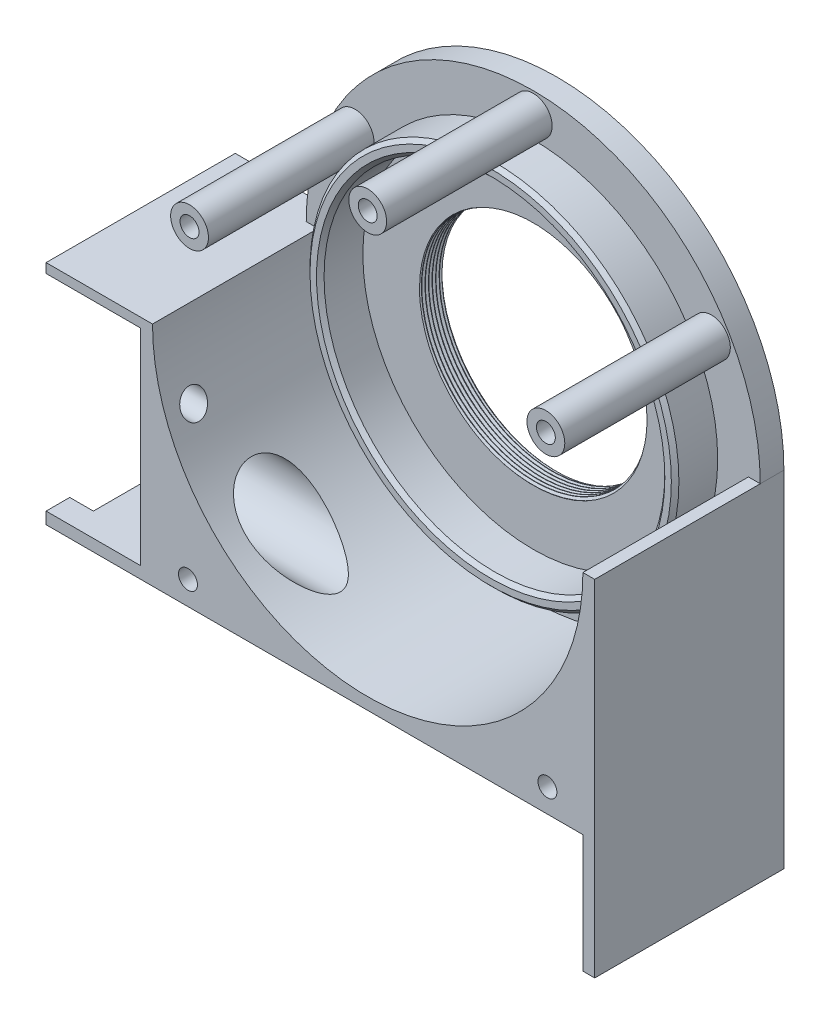
SolidWorks part; units mm, degrees
ref_plane "Plan de face" through (0, 0, 0) normal (0, 0, 1) x (1, 0, 0)
ref_plane "Plan de dessus" through (0, 0, 0) normal (0, 1, 0) x (1, 0, 0)
ref_plane "Plan de droite" through (0, 0, 0) normal (1, 0, 0) x (0, 0, -1)
sketch "Esquisse1" plane through (0, 0, 0) normal (0, 0, 1) x (1, 0, 0)
  circle A0 centre (0, 0) radius 23.8
  circle A1 centre (0, 0) radius 48
  dimension "D1" = 47.6
  dimension "D2" = 96
extrude "Boss.-Extru.1" add sketch "Esquisse1" along normal blind 40
sketch "Esquisse2" plane through (0, 0, 40) normal (0, 0, 1) x (1, 0, 0)
  circle A0 centre (0, 0) radius 45.5
  circle A1 centre (0, 0) radius 48 construction
  dimension "D1" = 2.5
extrude "Enlèv. mat.-Extru.1" cut sketch "Esquisse2" against normal blind 35
chamfer "Chanfrein2" distance 0.5 angle 45 1 edges at (23.8, 0, 0)
sketch "Esquisse14" plane through (0, 0, 0) normal (0, 0, 1) x (1, 0, 0)
  circle A0 centre (0, 0) radius 24.5
curve "Hélice/Spirale1" pitch 0.75 height 7.5 turns 10
sketch "Esquisse15" plane through (0, 0, 0) normal (-1, 0, 0) x (0, 0, 1)
  line L4 (0.501, -22.0731) -> (0.501, -22.5925) construction
  line L9 (0.8323, -23.8) -> (0.1698, -23.8)
  line L10 (0.1698, -23.8) -> (0.4573, -24.298)
  line L11 (0.4573, -24.298) -> (0.5448, -24.298)
  line L12 (0.8323, -23.8) -> (0.5448, -24.298)
  point P7 (0.501, -24.298)
  point P8 (0.501, -23.8)
  dimension "D1" = 60
  dimension "D2" = 0.0875
  dimension "D3" = 23.8
  dimension "D6" = 0.6625
sweep "Enlèvement de matière-Balayage1" cut profiles "Esquisse15" path "Hélice/Spirale1"
sketch "Esquisse23" plane through (0, 0, 40) normal (0, 0, 1) x (1, 0, 0)
  line L0 (-43.942, 0) -> (-49.526, 0)
  line L2 (43.942, 0) -> (49.526, 0)
  arc A0 (49.526, 0) -> (-49.526, 0) centre (0, 0) ccw
  arc A1 (43.942, 0) -> (-43.942, 0) centre (0, 0) ccw
extrude "Enlèv. mat.-Extru.6" cut sketch "Esquisse23" against normal up to surface (35 mm away) up to face at (-0.0839, -0.1997, 5)
sketch "Esquisse27" plane through (0, 0, 0) normal (1, 0, 0) x (0, 0, -1)
  circle A0 centre (-27.5, -34) radius 7.675
  dimension "D1" = 27.5
  dimension "D3" = 15.35
  dimension "D2" = 34
extrude "Enlèv. mat.-Extru.7" cut sketch "Esquisse27" against normal through all
sketch3d "Esquisse3D2" plane through (0, 0, 0) normal (0, 0, 1) x (1, 0, 0)
  dimension "D1" = 48
sketch "Esquisse33" plane through (-48, 0, 0) normal (1, 0, 0) x (0, 0, -1)
  line L0 (-24.2366, -37.2634) -> (-32.0205, -29.4795) construction
  line L1 (13.3219, -63.5082) -> (-63.8041, 13.6179) construction
  line L2 (-27.5, -34) -> (-32.3825, -38.8825) construction
  line L3 (-40, -48) -> (-40, 9.0935) construction
  line L5 (-40, -48) -> (0, -48)
  line L6 (-40, -48) -> (-40, 0)
  line L7 (-40, 0) -> (0, 0)
  line L8 (0, -48) -> (0, 0)
  circle A0 centre (-27.5, -34) radius 7.675
  circle A1 centre (-34.2175, -15.9688) radius 2.75
  circle A2 centre (-9.4688, -40.7175) radius 2.75
  dimension "D1" = 8
  dimension "D2" = 5.5
  dimension "D3" = 17.5
  dimension "D5" = 45
extrude "Boss.-Extru.5" add sketch "Esquisse33" along normal up to next
sketch "Esquisse35" plane through (-48, 0, 0) normal (-1, 0, 0) x (0, 0, 1)
  circle A0 centre (34.2175, -15.9688) radius 2.75
  circle A1 centre (9.4688, -40.7175) radius 2.75
extrude "Enlèv. mat.-Extru.12" cut sketch "Esquisse35" against normal blind 16
sketch "Esquisse36" plane through (-48, 0, 0) normal (-1, 0, 0) x (0, 0, 1)
  line L0 (2.5, 0) -> (0, 0)
  line L1 (0, 0) -> (5, 0) construction
  line L2 (0, 0) -> (0, -48)
  line L3 (0, -48) -> (0, 0) construction
  line L4 (0, -48) -> (40, -48)
  line L5 (40, -48) -> (0, -48) construction
  line L6 (40, -48) -> (40, -45.5)
  line L7 (40, -45.5) -> (2.5, -45.5)
  line L8 (2.5, -45.5) -> (2.5, 0)
  dimension "D1" = 2.5
extrude "Boss.-Extru.6" add sketch "Esquisse36" along normal blind 20
sketch "Esquisse37" plane through (0, -48, 0) normal (0, -1, 0) x (1, 0, 0)
  line L0 (0, 0) -> (0, 40) construction
  line L1 (-68, 0) -> (0, 0)
  line L2 (-68, 0) -> (-68, 2.5)
  line L3 (-68, 2.5) -> (0, 2.5)
  line L4 (0, 0) -> (0, 2.5)
  dimension "D1" = 2.5
extrude "Boss.-Extru.7" add sketch "Esquisse37" along normal blind 25
sketch "Esquisse43" plane through (0, 0, 40) normal (0, 0, 1) x (1, 0, 0)
  line L0 (0, -45.5) -> (0, -48)
  line L1 (45.5, 0) -> (48, 0)
  line L2 (48, 0) -> (48, -48)
  line L4 (0, -48) -> (48, -48)
  arc A0 (-45.5, 0) -> (45.5, 0) centre (0, 0) ccw construction
  arc A1 (0, -45.5) -> (45.5, 0) centre (0, 0) ccw
extrude "Boss.-Extru.10" add sketch "Esquisse43" against normal up to surface (40 mm away) up to face at (24.3, 0, 0)
sketch "Esquisse45" plane through (0, -48, 0) normal (0, -1, 0) x (1, 0, 0)
  line L0 (48, 0) -> (48, 40) construction
  line L1 (0, 0) -> (48, 0)
  line L2 (0, 0) -> (0, 2.5)
  line L3 (0, 2.5) -> (45.5, 2.5)
  line L4 (48, 0) -> (48, 2.5)
  line L5 (48, 40) -> (-68, 40) construction
  line L7 (48, 2.5) -> (48, 40)
  line L8 (48, 40) -> (45.5, 40)
  line L9 (45.5, 2.5) -> (45.5, 40)
  dimension "D1" = 2.5
extrude "Boss.-Extru.11" add sketch "Esquisse45" along normal up to surface (25 mm away) up to face at (-34, -73, 1.25)
sketch "Esquisse46" plane through (0, 0, 40) normal (0, 0, 1) x (1, 0, 0)
  line L0 (-58.2365, -43) -> (69.7757, -43) construction
  line L1 (45.5, -48) -> (-68, -48) construction
  line L2 (-48, -45.5) -> (-48, 0) construction
  line L3 (48, -73) -> (48, 0) construction
  circle A0 centre (-38, -43) radius 2
  circle A1 centre (38, -43) radius 2
  dimension "D2" = 4
  dimension "D3" = 10
  dimension "D4" = 4
  dimension "D5" = 10
  dimension "D1" = 5
extrude "Enlèv. mat.-Extru.14" cut sketch "Esquisse46" against normal blind 5
sketch "Esquisse47" plane through (0, 0, 5) normal (0, 0, 1) x (1, 0, 0)
  circle A0 centre (0, 0) radius 36.025
  circle A1 centre (0, 0) radius 39
  dimension "D1" = 72.05
  dimension "D2" = 78
extrude "Boss.-Extru.12" add sketch "Esquisse47" along normal blind 9
sketch "Esquisse48" plane through (0, -48, 0) normal (0, -1, 0) x (1, 0, 0)
  line L5 (-68, 21.25) -> (-31.7445, 21.25) construction
  line L6 (-68, 2.5) -> (-68, 40) construction
  line L7 (45.5, 40) -> (-68, 40) construction
  line L8 (-73, 7.5) -> (-63, 7.5)
  line L9 (-73, 7.5) -> (-73, 35)
  line L10 (-73, 35) -> (-63, 35)
  line L11 (-63, 7.5) -> (-63, 35)
  line L12 (-73, 7.5) -> (-63, 35) construction
  line L13 (-73, 35) -> (-63, 7.5) construction
  dimension "D1" = 5
  dimension "D2" = 5
extrude "Enlèv. mat.-Extru.15" cut sketch "Esquisse48" against normal blind 9
chamfer "Chanfrein3" distance 0.8 angle 45 2 edges at (36.025, 0, 14) (39, 0, 14)
sketch "Esquisse49" plane through (0, 0, 5) normal (0, 0, 1) x (1, 0, 0)
  line L0 (0, 0) -> (-55.4935, 32.0392) construction
  line L1 (-68, 0) -> (-48, 0) construction
  line L2 (0, 0) -> (-37.6721, 21.75) construction
  line L3 (0, 0) -> (0, 43.5) construction
  circle A0 centre (-37.6721, 21.75) radius 2
  circle A2 centre (-37.6721, 21.75) radius 4
  circle A3 centre (0, 43.5) radius 2
  circle A4 centre (0, 43.5) radius 4
  circle A5 centre (37.6721, 21.75) radius 2
  circle A6 centre (37.6721, 21.75) radius 4
  dimension "D2" = 4
  dimension "D3" = 8
  dimension "D1" = 30
  dimension "D4" = 43.5
  dimension "D6" = 60
  dimension "D5" = 3
extrude "Boss.-Extru.13" add sketch "Esquisse49" along normal blind 35
sketch "Esquisse50" plane through (-48, 0, 0) normal (-1, 0, 0) x (0, 0, 1)
  line L0 (2.5, -45.5) -> (2.5, 0) construction
  line L1 (40, 0) -> (2.5, 0)
  line L2 (40, 0) -> (40, -2)
  line L3 (40, -2) -> (2.5, -2)
  line L4 (2.5, 0) -> (2.5, -2)
  dimension "D1" = 2
extrude "Boss.-Extru.14" add sketch "Esquisse50" along normal up to surface (20 mm away) up to face at (-68, -41.625, 3.125)
